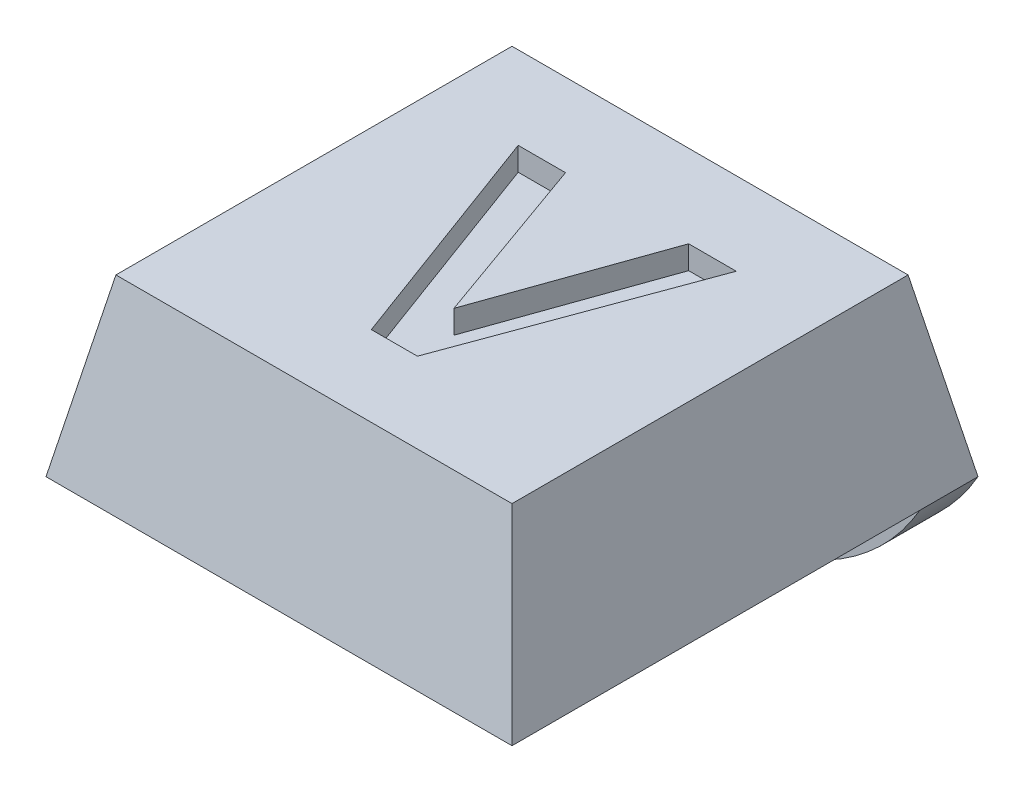
SolidWorks part; units mm, degrees
ref_plane "Front Plane" through (0, 0, 0) normal (0, 0, 1) x (1, 0, 0)
ref_plane "Top Plane" through (0, 0, 0) normal (0, 1, 0) x (1, 0, 0)
ref_plane "Right Plane" through (0, 0, 0) normal (1, 0, 0) x (0, 0, -1)
sketch "Sketch1" plane through (0, 0, 0) normal (0, 1, 0) x (1, 0, 0)
  line L1 (0, 0) -> (8, 0)
  line L2 (0, 0) -> (0, 8)
  line L3 (0, 8) -> (8, 8)
  line L4 (8, 0) -> (8, 8)
  dimension "D1" = 8
  dimension "D2" = 8
extrude "Boss-Extrude1" add sketch "Sketch1" along normal blind 3
sketch "Sketch2" plane through (0, 0, 0) normal (0, 0, 1) x (1, 0, 0)
  line L0 (0, 0) -> (0.6, 3)
  line L1 (0, 3) -> (8, 3) construction
  line L2 (0.6, 3) -> (0, 3)
  line L3 (0, 3) -> (0, 0)
  line L4 (8, 0) -> (7.4, 3)
  line L5 (7.4, 3) -> (8, 3)
  line L6 (8, 3) -> (8, 0)
  dimension "D1" = 0.6
  dimension "D2" = 0.6
extrude "Cut-Extrude1" cut sketch "Sketch2" against normal through all both and the other way through all
sketch "Sketch3" plane through (0, 0, 0) normal (1, 0, 0) x (0, 0, -1)
  line L0 (0, 0) -> (0.6, 3)
  line L1 (8, 3) -> (0, 3) construction
  line L2 (0.6, 3) -> (0, 3)
  line L3 (0, 3) -> (0, 0)
  line L4 (8, 3) -> (7.4, 3)
  line L5 (7.4, 3) -> (8, 0)
  line L6 (8, 3) -> (8, 0)
  dimension "D1" = 0.6
  dimension "D2" = 0.6
extrude "Cut-Extrude2" cut sketch "Sketch3" along normal blind 11
sketch "Sketch4" plane through (0, 0, 0) normal (0, -1, 0) x (1, 0, 0)
  line L0 (8, 0) -> (8, -8) construction
  line L3 (0, 0) -> (8, 0) construction
  circle A0 centre (4, -3.75) radius 1.75
  dimension "D1" = 3.5
  dimension "D2" = 4
  dimension "D3" = 3.75
extrude "Cut-Extrude3" cut sketch "Sketch4" against normal blind 0.4
sketch "Sketch5" plane through (0, 0, 0) normal (0, -1, 0) x (1, 0, 0)
  line L0 (8, 0) -> (8, -8) construction
  line L1 (0, -8) -> (8, -8)
  line L2 (0, -8) -> (0, -7)
  line L3 (0, -7) -> (8, -7)
  line L4 (8, -8) -> (8, -7)
  dimension "D1" = 1
extrude "Boss-Extrude2" add sketch "Sketch5" along normal blind 2
fillet "Fillet1" radius 4 2 edges at (8, -2, -7.5) (0, -2, -7.5)
sketch "Sketch6" plane through (0, 3, 0) normal (0, 1, 0) x (1, 0, 0)
  text T0 "V" font "Arial" height 4
extrude "Cut-Extrude4" cut sketch "Sketch6" against normal blind 0.4
